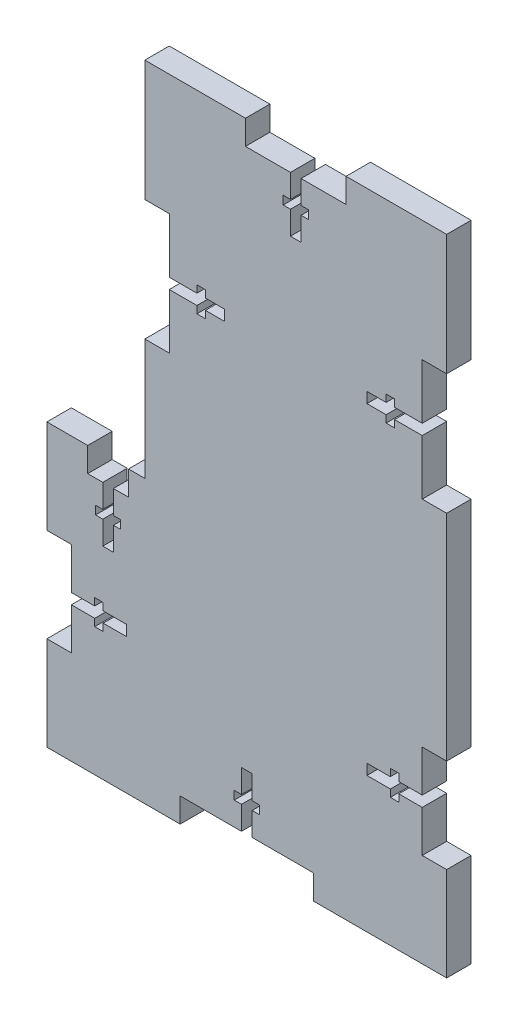
SolidWorks part; units mm, degrees
material "Mahogany"
ref_plane "Front Plane" through (0, 0, 0) normal (0, 0, 1) x (1, 0, 0)
ref_plane "Top Plane" through (0, 0, 0) normal (0, 1, 0) x (1, 0, 0)
ref_plane "Right Plane" through (0, 0, 0) normal (1, 0, 0) x (0, 0, -1)
sketch "Sketch1" plane through (0, 0, 0) normal (0, 0, 1) x (1, 0, 0)
  line L1 (-49.0474, -34.5694) -> (49.0474, -34.5694)
  line L2 (-49.0474, -34.5694) -> (-49.0474, 34.5694)
  line L3 (-49.0474, 34.5694) -> (49.0474, 34.5694)
  line L4 (49.0474, -34.5694) -> (49.0474, 34.5694)
  line L5 (-49.0474, -34.5694) -> (49.0474, 34.5694) construction
  line L6 (-49.0474, 34.5694) -> (49.0474, -34.5694) construction
  point P0 (0, 0)
  dimension "D1" = 98.0948
  dimension "D2" = 69.1388
extrude "Boss-Extrude1" add sketch "Sketch1" along normal blind 5.9944
sketch "Sketch2" plane through (0, 0, 5.9944) normal (0, 0, 1) x (1, 0, 0)
  line L1 (-39.0398, 34.5694) -> (-29.0322, 34.5694)
  line L2 (-39.0398, 34.5694) -> (-39.0398, 28.575)
  line L3 (-39.0398, 28.575) -> (-29.0322, 28.575)
  line L4 (-29.0322, 34.5694) -> (-29.0322, 28.575)
  line L5 (49.0474, 34.5694) -> (-49.0474, 34.5694) construction
  line L6 (0, 0) -> (49.0474, 0) construction
  line L7 (49.0474, -34.5694) -> (49.0474, 34.5694) construction
  dimension "D1" = 10.0076
  dimension "D2" = 5.9944
  dimension "D3" = 10.0076
extrude "Cut-Extrude1" cut sketch "Sketch2" against normal through all
sketch "Sketch3" plane through (0, 0, 5.9944) normal (0, 0, 1) x (1, 0, 0)
  line L0 (-49.0474, 34.5694) -> (-49.0474, -34.5694) construction
  line L1 (-49.0474, 11.5231) -> (-43.053, 11.5231)
  line L2 (-49.0474, 11.5231) -> (-49.0474, -11.5231)
  line L3 (-49.0474, -11.5231) -> (-43.053, -11.5231)
  line L4 (-43.053, 11.5231) -> (-43.053, -11.5231)
  line L5 (0, 0) -> (0, 39.951) construction
  line L6 (49.0474, -11.5231) -> (43.053, -11.5231)
  line L7 (49.0474, 11.5231) -> (49.0474, -11.5231)
  line L8 (49.0474, 11.5231) -> (43.053, 11.5231)
  line L9 (43.053, 11.5231) -> (43.053, -11.5231)
  dimension "D1" = 5.9944
  dimension "D2" = 23.0463
  dimension "D3" = 23.0463
extrude "Cut-Extrude2" cut sketch "Sketch3" against normal through all
sketch "Sketch4" plane through (0, 0, 5.9944) normal (0, 0, 1) x (1, 0, 0)
  line L0 (0, 0) -> (-43.053, 0) construction
  line L1 (-43.053, -11.5231) -> (-43.053, 11.5231) construction
  line L2 (0, 0) -> (0, 28.5152) construction
  line L3 (-43.053, 1.3017) -> (-29.4894, 1.3017)
  line L4 (-43.053, 1.3017) -> (-43.053, -1.3018)
  line L5 (-43.053, -1.3018) -> (-29.4894, -1.3018)
  line L6 (-29.4894, 1.3017) -> (-29.4894, -1.3018)
  line L7 (29.4894, 1.3018) -> (29.4894, -1.3018)
  line L8 (43.053, -1.3017) -> (29.4894, -1.3018)
  line L9 (43.053, 1.3017) -> (43.053, -1.3017)
  line L10 (43.053, 1.3017) -> (29.4894, 1.3018)
  line L11 (-49.0474, -11.5231) -> (-49.0474, 11.5231) construction
  point P9 (-29.4894, 0)
  dimension "D1" = 1.3017
  dimension "D2" = 19.558
extrude "Cut-Extrude3" cut sketch "Sketch4" against normal through all
sketch "Sketch5" plane through (0, 0, 5.9944) normal (0, 0, 1) x (1, 0, 0)
  line L0 (-34.036, 28.575) -> (-34.036, 4.7969) construction
  line L1 (-39.0398, 28.575) -> (-29.0322, 28.575) construction
  line L2 (0, 0) -> (35.9654, 0) construction
  line L3 (-32.7342, 28.575) -> (-35.3377, 28.575)
  line L4 (-32.7342, 28.575) -> (-32.7342, 15.0114)
  line L5 (-32.7342, 15.0114) -> (-35.3377, 15.0114)
  line L6 (-35.3377, 28.575) -> (-35.3377, 15.0114)
  point P11 (-34.036, 28.575)
  dimension "D1" = 2.6035
  dimension "D3" = 13.5636
extrude "Cut-Extrude4" cut sketch "Sketch5" against normal through all
sketch "Sketch6" plane through (0, 0, 5.9944) normal (0, 0, 1) x (1, 0, 0)
  line L0 (-36.2712, 1.3018) -> (-36.2712, -1.3018) construction
  line L1 (-29.4894, 1.3017) -> (-43.053, 1.3017) construction
  line L2 (-43.053, -1.3018) -> (-29.4894, -1.3018) construction
  line L3 (-32.7342, 21.7932) -> (-35.3377, 21.7932) construction
  line L4 (-32.7342, 28.575) -> (-32.7342, 15.0114) construction
  line L5 (-35.3377, 15.0114) -> (-35.3377, 28.575) construction
  line L6 (-32.7342, 21.7932) -> (-37.1221, 21.7932) construction
  line L7 (-37.1221, 22.8346) -> (-30.9499, 22.8346)
  line L8 (-37.1221, 22.8346) -> (-37.1221, 20.7518)
  line L9 (-37.1221, 20.7518) -> (-30.9499, 20.7518)
  line L10 (-30.9499, 22.8346) -> (-30.9499, 20.7518)
  line L11 (0, 0) -> (19.2929, 0) construction
  line L12 (0, 0) -> (0, 14.5303) construction
  line L17 (-36.2712, -1.3018) -> (-36.2712, -3.0861) construction
  line L18 (-37.3126, 3.0861) -> (-35.2298, 3.0861)
  line L19 (-37.3126, 3.0861) -> (-37.3126, -3.0861)
  line L20 (-37.3126, -3.0861) -> (-35.2298, -3.0861)
  line L21 (-35.2298, 3.0861) -> (-35.2298, -3.0861)
  line L22 (-34.036, 15.0114) -> (-34.036, 20.7518) construction
  line L23 (-32.7342, 15.0114) -> (-35.3377, 15.0114) construction
  line L24 (-29.4894, 0) -> (-35.2298, 0) construction
  line L25 (-29.4894, -1.3018) -> (-29.4894, 1.3017) construction
  line L26 (37.3126, -3.0861) -> (35.2298, -3.0861)
  line L27 (35.2298, 3.0861) -> (35.2298, -3.0861)
  line L28 (37.3126, 3.0861) -> (37.3126, -3.0861)
  line L29 (37.3126, 3.0861) -> (35.2298, 3.0861)
  dimension "D1" = 6.1722
  dimension "D2" = 2.0828
  dimension "D3" = 2.0828
  dimension "D4" = 6.1722
extrude "Cut-Extrude5" cut sketch "Sketch6" against normal through all
sketch "Sketch7" plane through (0, 0, 5.9944) normal (0, 0, 1) x (1, 0, 0)
  line L0 (49.0474, 34.5694) -> (49.0474, 123.4694)
  line L1 (49.0474, 123.4694) -> (-25.019, 123.4694)
  line L2 (-25.019, 123.4694) -> (-25.019, 34.5694)
  line L3 (49.0474, 34.5694) -> (-29.0322, 34.5694) construction
  line L60 (-32.7342, 22.8346) -> (-30.9499, 22.8346)
  line L61 (-30.9499, 22.8346) -> (-30.9499, 20.7518)
  line L62 (-30.9499, 20.7518) -> (-32.7342, 20.7518)
  line L63 (-32.7342, 15.0114) -> (-35.3377, 15.0114)
  line L64 (-35.3377, 20.7518) -> (-37.1221, 20.7518)
  line L65 (-37.1221, 20.7518) -> (-37.1221, 22.8346)
  line L66 (-37.1221, 22.8346) -> (-35.3377, 22.8346)
  line L67 (-35.3377, 28.575) -> (-39.0398, 28.575)
  line L68 (-32.7342, 28.575) -> (-32.7342, 22.8346)
  line L70 (-32.7342, 20.7518) -> (-32.7342, 15.0114)
  line L72 (43.053, -1.3018) -> (37.3126, -1.3018)
  line L73 (37.3126, -1.3018) -> (37.3126, -3.0861)
  line L74 (37.3126, -3.0861) -> (35.2298, -3.0861)
  line L75 (35.2298, -3.0861) -> (35.2298, -1.3017)
  line L76 (35.2298, -1.3017) -> (29.4894, -1.3017)
  line L77 (29.4894, -1.3017) -> (29.4894, 1.3018)
  line L78 (29.4894, 1.3018) -> (35.2298, 1.3018)
  line L79 (35.2298, 1.3018) -> (35.2298, 3.0861)
  line L80 (35.2298, 3.0861) -> (37.3126, 3.0861)
  line L81 (37.3126, 3.0861) -> (37.3126, 1.3018)
  line L82 (37.3126, 1.3018) -> (43.053, 1.3018)
  line L83 (43.053, 1.3018) -> (43.053, 11.5231)
  line L84 (43.053, 11.5231) -> (49.0474, 11.5231)
  line L85 (49.0474, 11.5231) -> (49.0474, 34.5694)
  line L86 (49.0474, 34.5694) -> (-29.0322, 34.5694)
  line L87 (-29.0322, 34.5694) -> (-29.0322, 28.575)
  line L88 (-29.0322, 28.575) -> (-32.7342, 28.575)
  line L89 (-35.3377, 15.0114) -> (-35.3377, 20.7518)
  line L91 (-35.3377, 22.8346) -> (-35.3377, 28.575)
  line L101 (-39.0398, 28.575) -> (-39.0398, 34.5694)
  line L102 (-39.0398, 34.5694) -> (-49.0474, 34.5694)
  line L103 (-49.0474, 34.5694) -> (-49.0474, 11.5231)
  line L104 (-49.0474, 11.5231) -> (-43.053, 11.5231)
  line L105 (-43.053, 11.5231) -> (-43.053, 1.3017)
  line L106 (-43.053, 1.3017) -> (-37.3126, 1.3017)
  line L107 (-37.3126, 1.3017) -> (-37.3126, 3.0861)
  line L108 (-37.3126, 3.0861) -> (-35.2298, 3.0861)
  line L109 (-35.2298, 3.0861) -> (-35.2298, 1.3017)
  line L110 (-35.2298, 1.3017) -> (-29.4894, 1.3017)
  line L111 (-29.4894, 1.3017) -> (-29.4894, -1.3018)
  line L112 (-29.4894, -1.3018) -> (-35.2298, -1.3018)
  line L113 (-35.2298, -1.3018) -> (-35.2298, -3.0861)
  line L114 (-35.2298, -3.0861) -> (-37.3126, -3.0861)
  line L115 (-37.3126, -3.0861) -> (-37.3126, -1.3018)
  line L116 (-37.3126, -1.3018) -> (-43.053, -1.3018)
  line L117 (-43.053, -1.3018) -> (-43.053, -11.5231)
  line L118 (-43.053, -11.5231) -> (-49.0474, -11.5231)
  line L119 (-49.0474, -11.5231) -> (-49.0474, -34.5694)
  line L120 (-49.0474, -34.5694) -> (49.0474, -34.5694)
  line L137 (49.0474, -34.5694) -> (49.0474, -11.5231)
  line L138 (49.0474, -11.5231) -> (43.053, -11.5231)
  line L139 (43.053, -11.5231) -> (43.053, -1.3018)
  line L154 (49.0474, 34.5694) -> (-25.019, 34.5694)
  dimension "D1" = 88.9
  dimension "D2" = 74.0664
  dimension "D3" = 0
extrude "Boss-Extrude2" add sketch "Sketch7" against normal blind 5.9944
sketch "Sketch8" plane through (0, 0, 5.9944) normal (0, 0, 1) x (1, 0, 0)
  line L0 (-49.0474, -34.5694) -> (49.0474, -34.5694) construction
  line L1 (16.3491, -34.5694) -> (-16.3491, -34.5694)
  line L2 (16.3491, -34.5694) -> (16.3491, -28.575)
  line L3 (16.3491, -28.575) -> (-16.3491, -28.575)
  line L4 (-16.3491, -34.5694) -> (-16.3491, -28.575)
  dimension "D1" = 5.9944
  dimension "D2" = 32.6983
  dimension "D3" = 32.6983
extrude "Cut-Extrude6" cut sketch "Sketch8" against normal through all
sketch "Sketch10" plane through (0, 0, 5.9944) normal (0, 0, 1) x (1, 0, 0)
  line L0 (16.3491, -28.575) -> (-16.3491, -28.575) construction
  line L1 (1.3017, -28.575) -> (-1.3017, -28.575)
  line L2 (1.3017, -28.575) -> (1.3017, -15.0114)
  line L3 (1.3017, -15.0114) -> (-1.3018, -15.0114)
  line L4 (-1.3017, -28.575) -> (-1.3018, -15.0114)
  line L5 (0, -15.0114) -> (0, 0) construction
  dimension "D1" = 2.6035
  dimension "D2" = 13.5636
extrude "Cut-Extrude7" cut sketch "Sketch10" against normal through all
sketch "Sketch11" plane through (0, 0, 5.9944) normal (0, 0, 1) x (1, 0, 0)
  line L0 (3.0861, -21.7932) -> (3.0861, -28.575) construction
  line L1 (16.3491, -28.575) -> (1.3017, -28.575) construction
  line L2 (-3.0861, -20.7518) -> (3.0861, -20.7518)
  line L3 (-3.0861, -20.7518) -> (-3.0861, -22.8346)
  line L4 (-3.0861, -22.8346) -> (3.0861, -22.8346)
  line L5 (3.0861, -20.7518) -> (3.0861, -22.8346)
  line L6 (-1.3018, -15.0114) -> (-1.3018, -28.575) construction
  point P8 (-1.3018, -22.8346)
  dimension "D1" = 2.0828
  dimension "D2" = 6.1722
  dimension "D3" = 6.7818
  dimension "D4" = 1.7844
extrude "Cut-Extrude8" cut sketch "Sketch11" against normal through all
sketch "Sketch12" plane through (0, 0, 5.9944) normal (0, 0, 1) x (1, 0, 0)
  line L0 (49.0474, 11.5231) -> (49.0474, 123.4694) construction
  line L1 (49.0474, 64.2027) -> (43.053, 64.2027)
  line L2 (49.0474, 64.2027) -> (49.0474, 93.8361)
  line L3 (49.0474, 93.8361) -> (43.053, 93.8361)
  line L4 (43.053, 64.2027) -> (43.053, 93.8361)
  line L5 (12.0142, 123.4694) -> (12.0142, 42.6911) construction
  line L6 (49.0474, 123.4694) -> (-25.019, 123.4694) construction
  line L7 (-19.0246, 64.2027) -> (-19.0246, 93.8361)
  line L8 (-25.019, 93.8361) -> (-19.0246, 93.8361)
  line L9 (-25.019, 64.2027) -> (-25.019, 93.8361)
  line L10 (-25.019, 64.2027) -> (-19.0246, 64.2027)
  dimension "D1" = 5.9944
  dimension "D2" = 29.6333
  dimension "D3" = 29.6333
extrude "Cut-Extrude9" cut sketch "Sketch12" against normal through all
sketch "Sketch13" plane through (0, 0, 5.9944) normal (0, 0, 1) x (1, 0, 0)
  line L0 (29.4894, 79.0194) -> (43.053, 79.0194) construction
  line L1 (43.053, 93.8361) -> (43.053, 64.2027) construction
  line L2 (12.0142, 123.4694) -> (12.0142, 63.8669) construction
  line L3 (49.0474, 123.4694) -> (-25.019, 123.4694) construction
  line L4 (-19.0246, 77.7177) -> (-19.0246, 80.3211)
  line L5 (29.4894, 77.7177) -> (43.053, 77.7177)
  line L6 (29.4894, 77.7177) -> (29.4894, 80.3212)
  line L7 (29.4894, 80.3212) -> (43.053, 80.3212)
  line L8 (43.053, 77.7177) -> (43.053, 80.3212)
  line L9 (-5.461, 80.3212) -> (-19.0246, 80.3211)
  line L10 (-5.461, 77.7177) -> (-5.461, 80.3212)
  line L11 (-5.461, 77.7177) -> (-19.0246, 77.7177)
  line L12 (12.0142, 130.1398) -> (12.0142, 123.4694) construction
  line L13 (13.316, 123.4694) -> (10.7125, 123.4694)
  line L14 (13.316, 123.4694) -> (13.316, 103.9114)
  line L15 (13.316, 103.9114) -> (10.7125, 103.9114)
  line L16 (10.7125, 123.4694) -> (10.7125, 103.9114)
  dimension "D1" = 2.6035
  dimension "D2" = 13.5636
  dimension "D3" = 2.6035
  dimension "D4" = 19.558
extrude "Cut-Extrude10" cut sketch "Sketch13" against normal through all
sketch "Sketch14" plane through (0, 0, 5.9944) normal (0, 0, 1) x (1, 0, 0)
  line L0 (36.2712, 93.7894) -> (43.053, 93.7894) construction
  line L1 (36.2712, 75.9333) -> (34.1884, 75.9333)
  line L2 (36.2712, 75.9333) -> (36.2712, 82.1055)
  line L3 (36.2712, 82.1055) -> (34.1884, 82.1055)
  line L4 (34.1884, 75.9333) -> (34.1884, 82.1055)
  line L5 (43.053, 93.8361) -> (43.053, 80.3212) construction
  line L6 (43.053, 80.3212) -> (29.4894, 80.3212) construction
  line L7 (12.0142, 123.4694) -> (12.0142, -38.735) construction
  line L9 (-12.2428, 82.1055) -> (-10.16, 82.1055)
  line L10 (-12.2428, 75.9333) -> (-12.2428, 82.1055)
  line L11 (-10.16, 75.9333) -> (-10.16, 82.1055)
  line L12 (-12.2428, 75.9333) -> (-10.16, 75.9333)
  line L14 (13.316, 123.4694) -> (10.7125, 123.4694) construction
  line L15 (10.7125, 123.4694) -> (10.7125, 103.9114) construction
  line L16 (15.1003, 109.6518) -> (8.9281, 109.6518)
  line L17 (15.1003, 109.6518) -> (15.1003, 111.7346)
  line L18 (15.1003, 111.7346) -> (8.9281, 111.7346)
  line L19 (8.9281, 109.6518) -> (8.9281, 111.7346)
  line L20 (8.9281, 110.6932) -> (8.9281, 123.4694) construction
  line L21 (10.7125, 123.4694) -> (-25.019, 123.4694) construction
  point P8 (34.1884, 80.3212)
  point P25 (10.7125, 109.6518)
  dimension "D1" = 2.0828
  dimension "D2" = 6.1722
  dimension "D3" = 6.7818
  dimension "D4" = 1.7844
  dimension "D5" = 2.0828
  dimension "D6" = 6.1722
  dimension "D7" = 1.7844
  dimension "D8" = 12.7762
extrude "Cut-Extrude11" cut sketch "Sketch14" against normal through all
sketch "Sketch15" plane through (0, 0, 5.9944) normal (0, 0, 1) x (1, 0, 0)
  line L0 (49.0474, 123.4694) -> (13.316, 123.4694) construction
  line L1 (24.3586, 123.4694) -> (-0.3302, 123.4694)
  line L2 (24.3586, 123.4694) -> (24.3586, 117.475)
  line L3 (24.3586, 117.475) -> (-0.3302, 117.475)
  line L4 (-0.3302, 123.4694) -> (-0.3302, 117.475)
  dimension "D1" = 5.9944
  dimension "D2" = 24.6888
  dimension "D3" = 24.6888
extrude "Cut-Extrude12" cut sketch "Sketch15" against normal through all
equation "\"Length\"= \"Length@Box.SLDASM\""
equation "\"D1@Sketch1\"  = \"Length\" + 2 * \"Material\""
equation "\"Width\"= \"Short Height@Box.SLDASM\""
equation "\"D2@Sketch1\" = \"Width\" + 2 * \"Material\""
equation "\"Material\"= \"Material@Box.SLDASM\""
equation "\"D1@Boss-Extrude1\" = \"Material\""
equation "\"D1@Sketch2\"=(\"Length\" -\"Over Hang@Box.SLDASM\"+\"Material\"*2)/3"
equation "\"D2@Sketch2\"= \"Material\""
equation "\"D3@Sketch2\"=(\"Length\" -\"Over Hang@Box.SLDASM\"+\"Material\"*2)/3"
equation "\"D1@Sketch3\"=\"Material\""
equation "\"D2@Sketch3\"=(\"Width\" +\"Material\"*2)/3"
equation "\"D3@Sketch3\"=(\"Width\" +\"Material\"*2)/3"
equation "\"Diameter of Screw\"= \"Diameter of Screw@Box.SLDASM\""
equation "\"Length of screw\"= \"Length of Screw@Box.SLDASM\""
equation "\"D3@Sketch5\"= \"Length of screw\" - \"Material\""
equation "\"D1@Sketch5\" = \"Diameter of Screw\""
equation "\"D1@Sketch4\"= \"Diameter of Screw\" /2"
equation "\"D2@Sketch4\"=\"Length of screw\""
equation "\"Diameter of Nut\"= \"Diameter of Nut@Box.SLDASM\""
equation "\"D1@Sketch6\"=\"Diameter of Nut\""
equation "\"Height of Nut\"= \"Height of Nut@Box.SLDASM\""
equation "\"D3@Sketch6\"= \"Height of Nut\""
equation "\"D4@Sketch6\"=\"Diameter of Nut\""
equation "\"D2@Sketch6\"=\"Height of Nut\""
equation "\"D1@Sketch7\"= \"Long Height@Box.SLDASM\"-\"Short Height@Box.SLDASM\""
equation "\"D2@Sketch7\" = \"Over Hang@Box.SLDASM\" + \"Material\""
equation "\"D1@Boss-Extrude2\" = \"Material\""
equation "\"D1@Sketch8\"= \"Material\""
equation "\"D2@Sketch8\"=(\"Length\" + \"Material\"*2)/3"
equation "\"D3@Sketch8\"=(\"Length\" + \"Material\"*2)/3"
equation "\"D1@Sketch10\"=\"Diameter of Screw\""
equation "\"D2@Sketch10\"=\"Length of screw\" - \"Material\""
equation "\"D3@Sketch11\" = ( \"Length of screw\" - \"Material\" ) / 2"
equation "\"D4@Sketch11\"= ( \"Diameter of Nut\"-\"Diameter of Screw\" )/2"
equation "\"D1@Sketch12\"=\"Material\""
equation "\"D2@Sketch12\"=(\"Long Height@Box.SLDASM\"-\"Short Height@Box.SLDASM\")/3"
equation "\"D3@Sketch12\"=(\"Long Height@Box.SLDASM\"-\"Short Height@Box.SLDASM\")/3"
equation "\"D1@Sketch13\"=\"Diameter of Screw\""
equation "\"D2@Sketch13\"=\"Length of screw\"-\"Material\""
equation "\"D1@Sketch14\"=\"Height of Nut\""
equation "\"D2@Sketch14\"=\"Diameter of Nut\""
equation "\"D3@Sketch14\"=(\"Length of screw\"-\"Material\")/2"
equation "\"D4@Sketch14\"=(\"Diameter of Nut\"-\"Diameter of Screw\")/2"
equation "\"D1@Sketch15\"= \"Material\""
equation "\"D2@Sketch15\"=(\"Material\"+ \"over hang@Box.SLDASM\" )/3"
equation "\"D3@Sketch15\"=(\"Material\" + \"over hang@Box.SLDASM\" )/3"
equation "\"D3@Sketch13\"=\"Diameter of Screw\""
equation "\"D4@Sketch13\"=\"Length of screw\""
equation "\"D5@Sketch14\"=\"Height of Nut\""
equation "\"D6@Sketch14\"=\"Diameter of Nut\""
equation "\"D7@Sketch14\"=(\"Diameter of Nut\"-\"Diameter of Screw\")/2"
equation "\"D8@Sketch14\"=(\"Length of screw\"-\"Material\")/2 + \"Material\""
